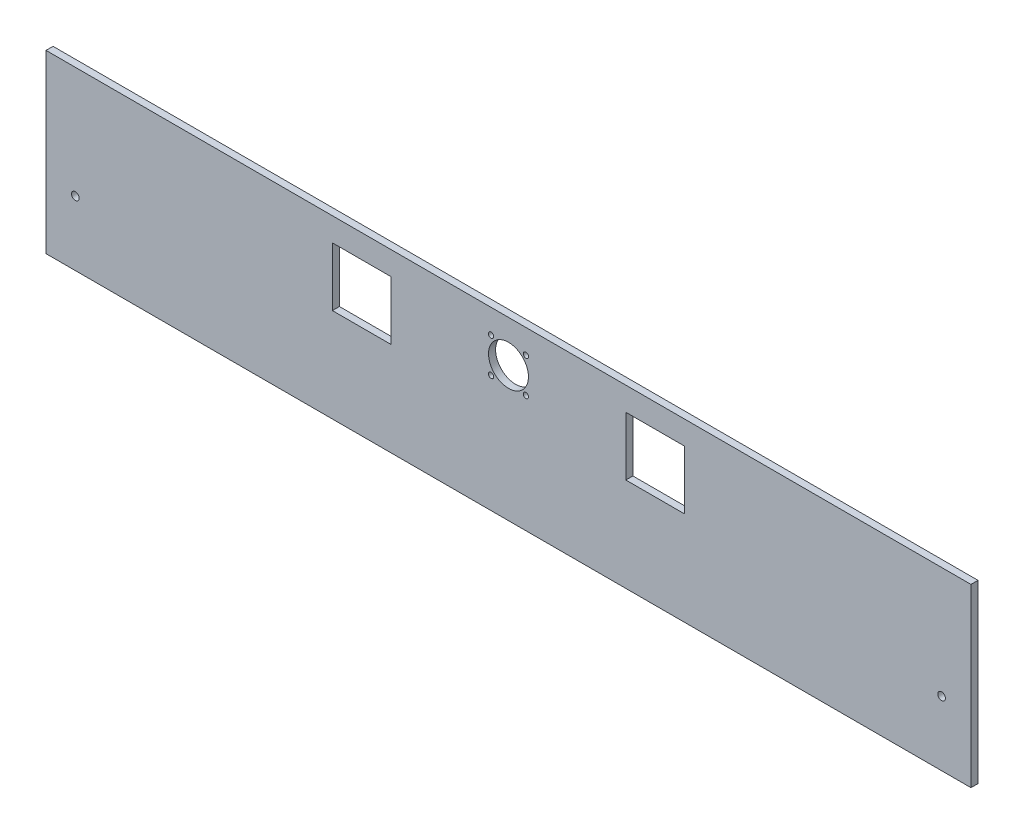
SolidWorks part; units mm, degrees
note: The reader was unsure of these and kept them because the rebuilt part matched: thickness of "Base-Flange1", "Sheet-Metal1", "Sheet-Metal2", "Sheet-Metal3".
ref_plane "Front Plane" through (0, 0, 0) normal (0, 0, 1) x (1, 0, 0)
ref_plane "Top Plane" through (0, 0, 0) normal (0, 1, 0) x (1, 0, 0)
ref_plane "Right Plane" through (0, 0, 0) normal (1, 0, 0) x (0, 0, -1)
sketch "Sketch1" plane through (0, 0, 0) normal (0, 0, 1) x (1, 0, 0)
  line L1 (-394, -75) -> (394, -75)
  line L2 (-394, -75) -> (-394, 75)
  line L3 (-394, 75) -> (394, 75)
  line L4 (394, -75) -> (394, 75)
  line L5 (-394, -75) -> (394, 75) construction
  line L6 (-394, 75) -> (394, -75) construction
  point P0 (0, 0)
  dimension "D1" = 150
  dimension "D2" = 788
base flange "Base-Flange1" sketch "Sketch1" thickness 6 reverse thickness direction no parameters "D1"=2
sketch "Sketch2" plane through (0, 0, 0) normal (0, 0, 1) x (1, 0, 0)
  line L0 (0, 0) -> (0, 39.65) construction
  line L1 (-14.8492, 24.8008) -> (14.8492, 24.8008) construction
  line L2 (-14.8492, 24.8008) -> (-14.8492, 54.4992) construction
  line L3 (-14.8492, 54.4992) -> (14.8492, 54.4992) construction
  line L4 (14.8492, 24.8008) -> (14.8492, 54.4992) construction
  line L5 (-14.8492, 24.8008) -> (14.8492, 54.4992) construction
  line L6 (-14.8492, 54.4992) -> (14.8492, 24.8008) construction
  line L7 (394, 75) -> (-394, 75) construction
  line L8 (-125, 30) -> (125, 30) construction
  line L9 (-150, 5) -> (-100, 5)
  line L10 (-150, 5) -> (-150, 55)
  line L11 (-150, 55) -> (-100, 55)
  line L12 (-100, 5) -> (-100, 55)
  line L13 (-150, 5) -> (-100, 55) construction
  line L14 (-150, 55) -> (-100, 5) construction
  line L15 (100, 5) -> (150, 5)
  line L16 (100, 5) -> (100, 55)
  line L17 (100, 55) -> (150, 55)
  line L18 (150, 5) -> (150, 55)
  line L19 (100, 5) -> (150, 55) construction
  line L20 (100, 55) -> (150, 5) construction
  line L21 (0, 30) -> (0, 0) construction
  circle A0 centre (14.8492, 54.4992) radius 2.25
  circle A1 centre (-14.8492, 54.4992) radius 2.25
  circle A2 centre (-14.8492, 24.8008) radius 2.25
  circle A3 centre (14.8492, 24.8008) radius 2.25
  circle A4 centre (0, 39.65) radius 17
  point P0 (0, 39.65)
  point P14 (-125, 30)
  point P19 (125, 30)
  dimension "D2" = 4.5
  dimension "D7" = 34
  dimension "D1" = 42
  dimension "D3" = 35.35
  dimension "D4" = 70
  dimension "D5" = 50
  dimension "D6" = 200
extrude "Cut-Extrude1" cut sketch "Sketch2" against normal through all
sketch "Sketch3" plane through (0, 0, 0) normal (0, 0, 1) x (1, 0, 0)
  line L0 (-369, -20) -> (369, -20) construction
  line L1 (0, 0) -> (0, -20) construction
  line L2 (394, 75) -> (-394, 75) construction
  line L3 (394, -75) -> (394, 75) construction
  circle A0 centre (369, -20) radius 3.25
  circle A1 centre (-369, -20) radius 3.25
  point P3 (0, -20)
  dimension "D3" = 6.5
  dimension "D4" = 6.5
  dimension "D1" = 95
  dimension "D2" = 25
extrude "Cut-Extrude2" cut sketch "Sketch3" against normal blind 10
sketch "Bend-Lines1" [suppressed] plane through (0, 0, 0) normal (0, 1, 0) x (1, 0, 0)
sketch "Bounding-Box1" [suppressed] plane through (0, 0, 0) normal (0, 1, 0) x (1, 0, 0)
sheet metal parameters "Sheet-Metal1" thickness 6 parameters "D1"=2, "D7"=1.5
flat pattern "Flat-Pattern1" [suppressed]
sketch "Bend-Lines2" plane through (0, 0, 0) normal (0, 1, 0) x (1, 0, 0)
sketch3d "Bounding-Box2" [suppressed]
  line L0 (-400, -75, 0) -> (400, -75, 0) construction
  line L1 (-400, 75, 0) -> (400, 75, 0) construction
  line L2 (-400, -75, 0) -> (-400, 75, 0) construction
  line L3 (400, -75, 0) -> (400, 75, 0) construction
sheet metal parameters "Sheet-Metal2" thickness 6 parameters "D1"=2, "D7"=1.5
flat pattern "Flat-Pattern1"
sketch "Bend-Lines2" plane through (0, 0, 0) normal (0, 1, 0) x (1, 0, 0)
sketch3d "Bounding-Box2" [suppressed]
  line L0 (-394, -75, 0) -> (394, -75, 0) construction
  line L1 (-394, 75, 0) -> (394, 75, 0) construction
  line L2 (-394, -75, 0) -> (-394, 75, 0) construction
  line L3 (394, -75, 0) -> (394, 75, 0) construction
sheet metal parameters "Sheet-Metal3" thickness 6 parameters "D1"=2, "D7"=1.5
flat pattern "Flat-Pattern1"
sketch "Bend-Lines2" plane through (0, 0, 0) normal (0, 1, 0) x (1, 0, 0)
sketch3d "Bounding-Box2" [suppressed]
  line L0 (-394, -75, 0) -> (394, -75, 0) construction
  line L1 (-394, 75, 0) -> (394, 75, 0) construction
  line L2 (-394, -75, 0) -> (-394, 75, 0) construction
  line L3 (394, -75, 0) -> (394, 75, 0) construction
